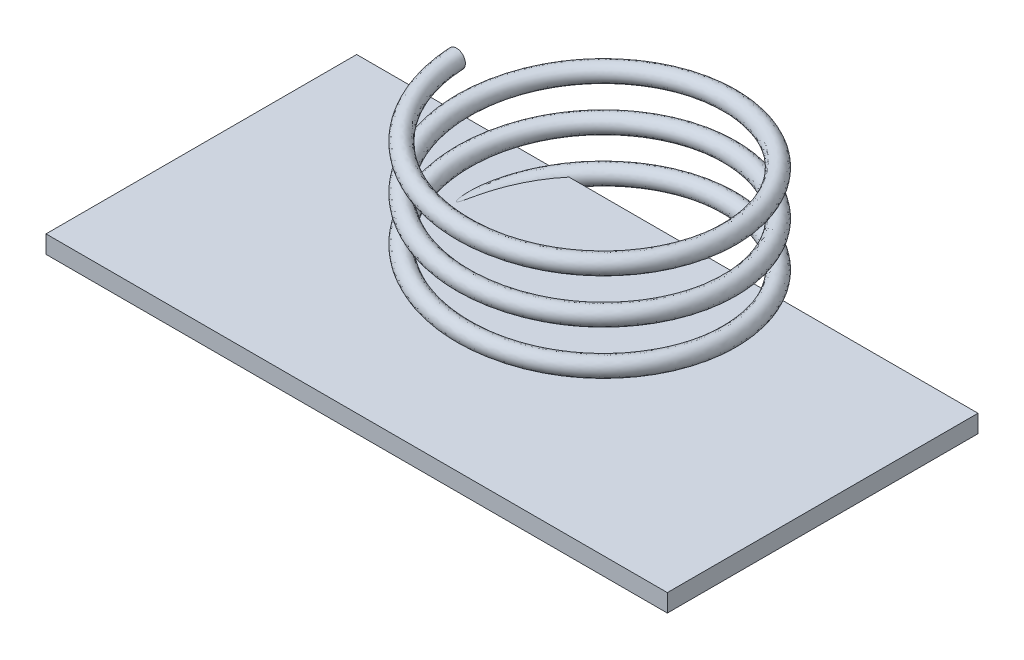
SolidWorks part; units mm, degrees
ref_plane "Front Plane" through (0, 0, 0) normal (0, 0, 1) x (1, 0, 0)
ref_plane "Top Plane" through (0, 0, 0) normal (0, 1, 0) x (1, 0, 0)
ref_plane "Right Plane" through (0, 0, 0) normal (1, 0, 0) x (0, 0, -1)
sketch "Sketch6" plane through (0, 0, 0) normal (0, 1, 0) x (1, 0, 0)
  circle A0 centre (0, 0) radius 3
curve "Helix/Spiral2" pitch 1 height 3 radius 3 left hand yes centre (0, 0, 0) axis (0, 1, 0) start towards (0, 0, 1)
sketch "Sketch7" plane through (0, 0, 0) normal (0, 0, 1) x (1, 0, 0)
  circle A0 centre (-3, 0) radius 0.2
  spline S0 degree 3 poles (-3, 0) (-3, 0.0207) (-2.8438, 0.0626) (-2.1765, 0.125) (-1.1779, 0.1875) (0, 0.25) (1.1779, 0.3125) (2.1765, 0.375) (2.8438, 0.4375) (3.0781, 0.5) (2.8438, 0.5625) (2.1765, 0.625) (0.8451, 0.7083) (-0.8451, 0.7917) (-2.1765, 0.875) (-2.8438, 0.9375) (-3.0781, 1) (-2.8438, 1.0625) (-2.1765, 1.125) (-0.8451, 1.2083) (0.8451, 1.2917) (2.1765, 1.375) (2.8438, 1.4375) (3.0781, 1.5) (2.8438, 1.5625) (2.1765, 1.625) (0.8451, 1.7083) (-0.8451, 1.7917) (-2.1765, 1.875) (-2.8438, 1.9375) (-3.0781, 2) (-2.8438, 2.0625) (-2.1765, 2.125) (-0.8451, 2.2083) (0.8451, 2.2917) (2.1765, 2.375) (2.8438, 2.4375) (3.0781, 2.5) (2.8438, 2.5625) (2.1765, 2.625) (1.1779, 2.6875) (0, 2.75) (-1.1779, 2.8125) (-2.1765, 2.875) (-2.8438, 2.9374) (-3, 2.9793) (-3, 3) knots 0 0 0 0 0.020833 0.041667 0.0625 0.083333 0.104167 0.125 0.145833 0.166667 0.1875 0.208333 0.229167 0.270833 0.291667 0.3125 0.333333 0.354167 0.375 0.395833 0.4375 0.458333 0.479167 0.5 0.520833 0.541667 0.5625 0.604167 0.625 0.645833 0.666667 0.6875 0.708333 0.729167 0.770833 0.791667 0.8125 0.833333 0.854167 0.875 0.895833 0.916667 0.9375 0.958333 0.979167 1 1 1 1 construction
sweep "Sweep1" add profiles "Sketch7" path "Helix/Spiral2"
sketch "Sketch8" plane through (0, 0, 0) normal (0, 1, 0) x (1, 0, 0)
  line L0 (0, 0) -> (0, -1.75) construction
  line L2 (-7, 1.75) -> (7, 1.75)
  line L3 (-7, 1.75) -> (-7, -5.25)
  line L4 (-7, -5.25) -> (7, -5.25)
  line L5 (7, 1.75) -> (7, -5.25)
  line L6 (-7, 1.75) -> (7, -5.25) construction
  line L7 (-7, -5.25) -> (7, 1.75) construction
extrude "Boss-Extrude2" add sketch "Sketch8" against normal blind 0.2 and the other way blind 0.2
